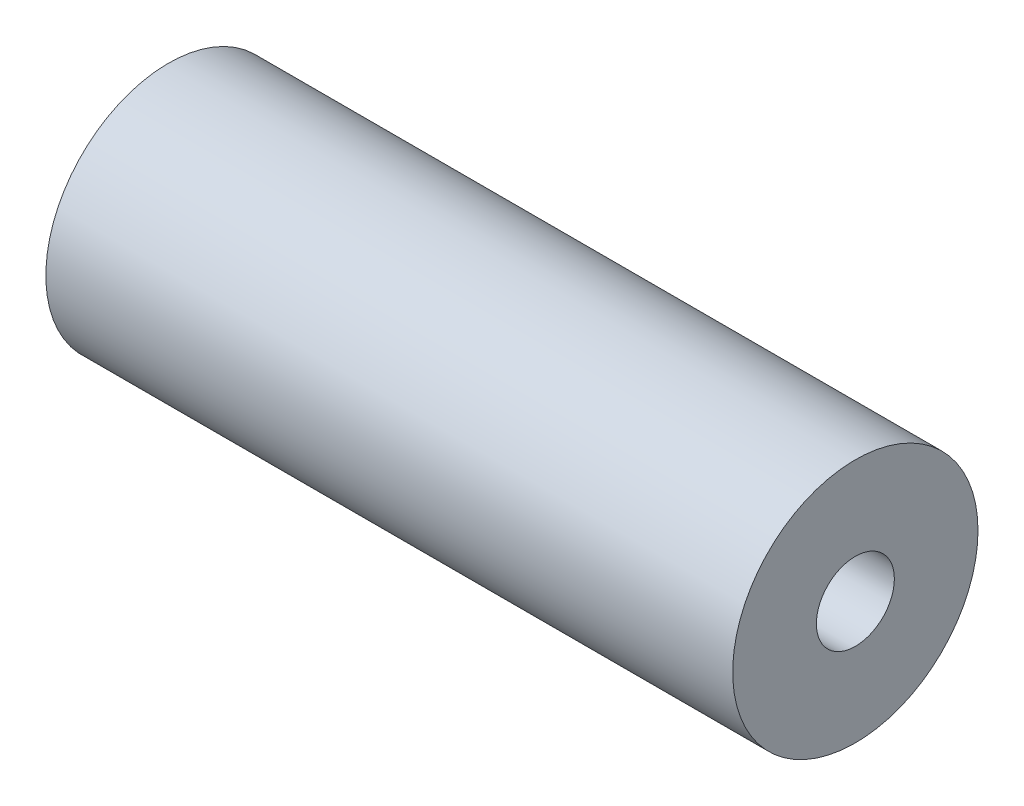
SolidWorks part; units mm, degrees
material "6061-T6 (SS)"
ref_plane "Front Plane" through (0, 0, 0) normal (0, 0, 1) x (1, 0, 0)
ref_plane "Top Plane" through (0, 0, 0) normal (0, 1, 0) x (1, 0, 0)
ref_plane "Right Plane" through (0, 0, 0) normal (1, 0, 0) x (0, 0, -1)
sketch "Sketch1" plane through (0, 0, 0) normal (1, 0, 0) x (0, 0, -1)
  circle A0 centre (0, 0) radius 6.35
  dimension "D1" = 12.7
extrude "Boss-Extrude1" add sketch "Sketch1" along normal mid plane 35.56
hole_wizard "Tap Drill for #10-32 Tap1" positions "Sketch2" profile "Sketch4" hole size "#10-32" standard "ANSI Inch"
sketch "Sketch2" plane through (17.78, 0, 0) normal (1, 0, 0) x (0, 0, -1)
  point P0 (0, 0)
sketch "Sketch4" plane through (17.78, 0, 0) normal (0, 1, 0) x (0, 0, -1)
  line L0 (0, 0) -> (0, 12.6433)
  line L1 (0, 12.6433) -> (2.0193, 11.43)
  line L2 (2.0193, 11.43) -> (2.0193, 0)
  line L5 (2.0193, 0) -> (0, 0)
  line L10 (0, 12.6433) -> (-2.0193, 11.43) construction
  line L11 (0, -6.35) -> (0, 107.95) construction
  dimension "Hole Dia." = 4.0386
  dimension "Hole Depth" = 11.43
  dimension "Drill Angle" = 118
mirror "Mirror1" about plane through (0, 0, 0) normal (1, 0, 0) of "Tap Drill for #10-32 Tap1"
